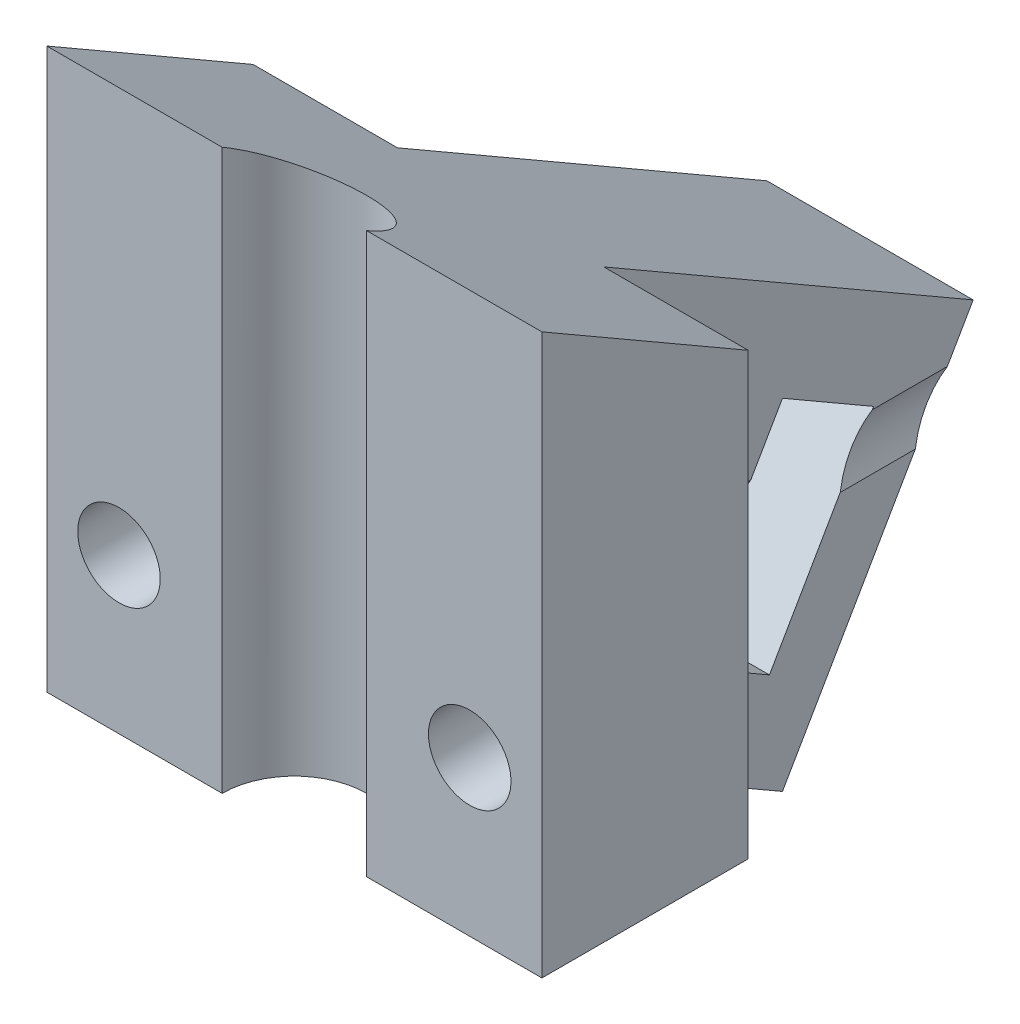
SolidWorks part; units mm, degrees
ref_plane "Спереди" through (0, 0, 0) normal (0, 0, 1) x (1, 0, 0)
ref_plane "Сверху" through (0, 0, 0) normal (0, 1, 0) x (1, 0, 0)
ref_plane "Справа" through (0, 0, 0) normal (1, 0, 0) x (0, 0, -1)
sketch "Эскиз1" plane through (0, 0, 0) normal (0, 1, 0) x (1, 0, 0)
  line L1 (-24, -10) -> (24, -10)
  line L2 (-24, -10) -> (-24, 10)
  line L3 (-24, 10) -> (24, 10)
  line L4 (24, -10) -> (24, 10)
  line L5 (-24, -10) -> (24, 10) construction
  line L6 (-24, 10) -> (24, -10) construction
  point P0 (0, 0)
  dimension "D1" = 48
  dimension "D2" = 20
extrude "Бобышка-Вытянуть1" add sketch "Эскиз1" along normal blind 30
sketch "Эскиз2" plane through (0, 0, 10) normal (0, 0, 1) x (1, 0, 0)
  line L0 (-7, 30) -> (-7, 0)
  line L1 (-24, 30) -> (24, 30) construction
  line L2 (-24, 0) -> (24, 0) construction
  line L3 (-7, 0) -> (7, 0)
  line L4 (7, 0) -> (7, 30)
  line L5 (7, 30) -> (-7, 30)
  dimension "D1" = 17
  dimension "D2" = 14
extrude "Вырез-Вытянуть1" cut sketch "Эскиз2" against normal blind 7
sketch "Эскиз7" plane through (24, 0, 0) normal (1, 0, 0) x (0, 0, -1)
  line L0 (10, 0) -> (27.3205, -10) construction
  line L3 (-10, 0) -> (10, 0)
  line L4 (10, 0) -> (27.3205, -10)
  line L5 (10, 30) -> (32, 30)
  line L6 (32, 30) -> (45.8109, 22.0263)
  line L7 (27.3205, -10) -> (45.8109, 22.0263)
  line L8 (10, 0) -> (10, 30)
  line M4 (10, 0) -> (10, 30)
  dimension "D1" = 150
  dimension "D2" = 20
  dimension "D3" = 22
extrude "Бобышка-Вытянуть2" add sketch "Эскиз7" against normal blind 48 contours L4 L7 L6 L5 M4 region at (24, 13.2668, -24.7301)
sketch "Эскиз8" plane through (24, 0, 0) normal (1, 0, 0) x (0, 0, -1)
  line L0 (10, 0) -> (10, 30)
  line L1 (-10, 30) -> (32, 30) construction
  line L2 (10, 30) -> (32, 30)
  line L3 (32, 30) -> (45.8109, 22.0263)
  line L4 (45.8109, 22.0263) -> (27.3205, -10)
  line L5 (27.3205, -10) -> (10, 0)
extrude "Вырез-Вытянуть2" cut sketch "Эскиз8" against normal blind 14
sketch "Эскиз9" plane through (-24, 0, 0) normal (-1, 0, 0) x (0, 0, 1)
  line L0 (-10, 0) -> (-10, 30)
  line L1 (-32, 30) -> (10, 30) construction
  line L2 (-10, 30) -> (-32, 30)
  line L3 (-32, 30) -> (-45.8109, 22.0263)
  line L4 (-45.8109, 22.0263) -> (-27.3205, -10)
  line L5 (-27.3205, -10) -> (-10, 0)
extrude "Вырез-Вытянуть3" cut sketch "Эскиз9" against normal blind 14
sketch "Эскиз11" plane through (-10, 0, 0) normal (-1, 0, 0) x (0, 0, 1)
  line L0 (-36.449, 27.4314) -> (-16.9282, -4) construction
  line L1 (-27.3205, -10) -> (-10, 0) construction
  line L3 (-17.2219, 5.5188) -> (-27.3219, 23.0125)
  line L5 (-32, 30) -> (-45.8109, 22.0263) construction
  line L6 (-17.2219, 5.5188) -> (-26.0553, 0.4188)
  line L7 (-27.3219, 23.0125) -> (-36.1553, 17.9125)
  line L8 (-26.0553, 0.4188) -> (-36.1553, 17.9125)
  line L9 (-17.2219, 5.5188) -> (-36.1553, 17.9125) construction
  line L10 (-27.3219, 23.0125) -> (-26.0553, 0.4188) construction
  point P7 (-26.6886, 11.7157)
  point P8 (-26.6886, 11.7157)
  dimension "D1" = 20.2
  dimension "D2" = 10.2
  dimension "D3" = 12
extrude "Вырез-Вытянуть4" cut sketch "Эскиз11" against normal through all
sketch "Эскиз13" plane through (0, 0, -10) normal (0, 0, -1) x (-1, 0, 0)
  line L0 (24, 15) -> (10, 15) construction
  line L1 (24, 0) -> (24, 30) construction
  line L2 (10, 0) -> (10, 30) construction
  circle A0 centre (17, 15) radius 4
extrude "Вырез-Вытянуть5" cut sketch "Эскиз13" against normal through all
sketch "Эскиз14" plane through (0, 0, -10) normal (0, 0, -1) x (-1, 0, 0)
  line L0 (-24, 15) -> (-10, 15) construction
  line L1 (-24, 30) -> (-24, 0) construction
  line L2 (-10, 30) -> (-10, 0) construction
  circle A0 centre (-17, 15) radius 4
extrude "Вырез-Вытянуть6" cut sketch "Эскиз14" against normal through all
fillet "Скругление1" radius 7 2 edges at (-7, 15, 3) (7, 15, 3)
sketch "Эскиз18" plane through (0, -14.3301, -24.8205) normal (0, -0.5, -0.866) x (-1, 0, 0)
  line L0 (-10, 23.4904) -> (10, 23.4904) construction
  line L1 (-10, 5) -> (-10, 41.9808) construction
  line L2 (10, 41.9808) -> (10, 5) construction
  text T0 "L" font "Arial" height 8
extrude "Бобышка-Вытянуть5" add sketch "Эскиз18" along normal blind 1
sketch "Эскиз20" plane through (0, 0, -10) normal (0, 0, -1) x (-1, 0, 0)
  circle A0 centre (-17, 15) radius 7.5
  circle A1 centre (17, 15) radius 7.5
  dimension "D1" = 15
extrude "Вырез-Вытянуть8" cut sketch "Эскиз20" along normal through all
sketch "Sketch3" plane through (0, 30, 0) normal (0, 1, 0) x (1, 0, 0)
  line L0 (7, -10) -> (24, -10)
  line L1 (24, -10) -> (24, 10)
  line L2 (24, 10) -> (10, 10)
  line L3 (10, 10) -> (10, 32)
  line L4 (10, 32) -> (-10, 32)
  line L5 (-10, 32) -> (-10, 10)
  line L6 (-10, 10) -> (-24, 10)
  line L7 (-24, 10) -> (-24, -10)
  line L8 (-24, -10) -> (-7, -10)
  arc A0 (-7, -10) -> (7, -10) centre (0, -10) cw
extrude "Boss-Extrude1" add sketch "Sketch3" along normal blind 25
sketch "Sketch4" plane through (-10, 0, 0) normal (-1, 0, 0) x (0, 0, 1)
  line L0 (-45.8109, 22.0263) -> (35.6307, 69.0466)
  line L1 (-32, 30) -> (-45.8109, 22.0263) construction
extrude "Cut-Extrude1" cut sketch "Sketch4" against normal through all both and the other way through all
